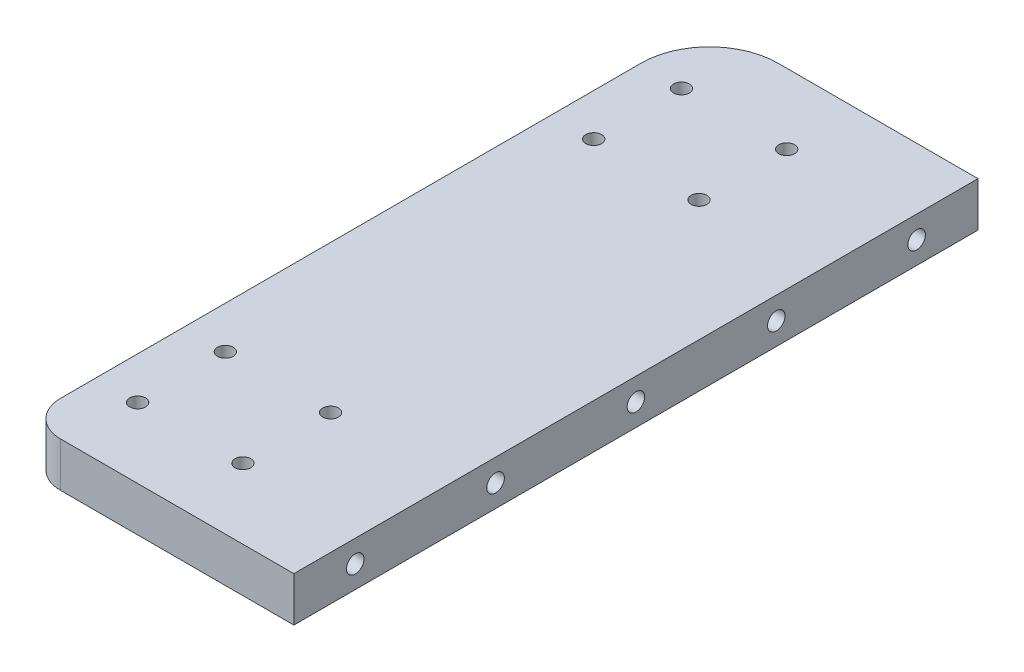
SolidWorks part; units mm, degrees
ref_plane "Front Plane" through (0, 0, 0) normal (0, 0, 1) x (1, 0, 0)
ref_plane "Top Plane" through (0, 0, 0) normal (0, 1, 0) x (1, 0, 0)
ref_plane "Right Plane" through (0, 0, 0) normal (1, 0, 0) x (0, 0, -1)
sketch "Sketch1" plane through (0, 0, 0) normal (0, 1, 0) x (1, 0, 0)
  line L0 (43.025, 97.5) -> (43.025, -97.5)
  line L4 (-33.5, 77.975) -> (-33.5, -87.5)
  line L5 (43.025, 97.5) -> (-40.2179, -91.1388) construction
  line L6 (43.025, -97.5) -> (-40.2179, 91.1388) construction
  line L7 (-13.975, 97.5) -> (43.025, 97.5)
  line L8 (-23.5, -97.5) -> (43.025, -97.5)
  circle A0 centre (-21.5, -77.5) radius 2.25
  circle A1 centre (8.5, -77.5) radius 2.25
  circle A2 centre (8.5, -52.5) radius 2.25
  circle A3 centre (-21.5, -52.5) radius 2.25
  circle A4 centre (-21.5, 52.5) radius 2.25
  circle A5 centre (-21.5, 77.5) radius 2.25
  circle A6 centre (8.5, 77.5) radius 2.25
  circle A7 centre (8.5, 52.5) radius 2.25
  arc A8 (-23.5, -97.5) -> (-33.5, -87.5) centre (-23.5, -87.5) cw
  arc A11 (-13.975, 97.5) -> (-33.5, 77.975) centre (-13.975, 77.975) ccw
  point P0 (0, 0)
  point P5 (-21.5, -52.5)
  point P6 (8.5, -52.5)
  point P8 (8.5, -77.5)
  point P9 (-21.5, -77.5)
  dimension "D8" = 4.5
  dimension "D9" = 4.5
  dimension "D10" = 4.5
  dimension "D11" = 4.5
  dimension "D12" = 10
  dimension "D13" = 20
  dimension "D1" = 25
  dimension "D2" = 30
  dimension "D3" = 195
  dimension "D4" = 195
  dimension "D5" = 66.525
  dimension "D7" = 12
  dimension "D14" = 57
  dimension "D15" = 8.5
  dimension "D16" = 40.2179
  dimension "D17" = 52.5
  dimension "D6" = 2
extrude "Boss-Extrude1" add sketch "Sketch1" along normal blind 12.7
sketch "Sketch2" plane through (43.025, 0, 0) normal (1, 0, 0) x (0, 0, -1)
  line L0 (-97.5, 0) -> (97.5, 0) construction
  line L1 (-97.5, 12.7) -> (-97.5, 0) construction
  point P0 (-80, 6.35)
  point P5 (-40, 6.35)
  point P7 (0, 6.35)
  point P8 (40, 6.35)
  point P9 (80, 6.35)
  dimension "D1" = 6.35
  dimension "D2" = 17.5
  dimension "D3" = 5
hole_wizard "Tap Drill for M6x1.0 Tap1" positions "Sketch2" profile "Sketch3" hole size "M6x1.0" standard "ANSI Metric"
sketch "Sketch3" plane through (43.025, 6.35, 80) normal (0, 1, 0) x (0, 0, -1)
  line L0 (0, 0) -> (0, 18.5022)
  line L1 (0, 18.5022) -> (2.5, 17)
  line L2 (2.5, 17) -> (2.5, 0)
  line L5 (2.5, 0) -> (0, 0)
  line L10 (0, 18.5022) -> (-2.5, 17) construction
  line L11 (0, -6.35) -> (0, 107.95) construction
  dimension "Hole Dia." = 5
  dimension "Hole Depth" = 17
  dimension "Drill Angle" = 118
